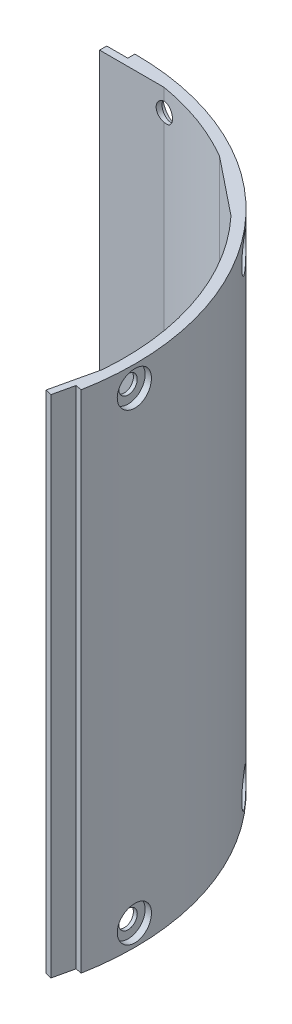
SolidWorks part; units mm, degrees
ref_plane "Спереди" through (0, 0, 0) normal (0, 0, 1) x (1, 0, 0)
ref_plane "Сверху" through (0, 0, 0) normal (0, 1, 0) x (1, 0, 0)
ref_plane "Справа" through (0, 0, 0) normal (1, 0, 0) x (0, 0, -1)
sketch "Эскиз2" plane through (0, 0, 0) normal (0, 1, 0) x (1, 0, 0)
  line L0 (0, -1000) -> (0, 49000) construction
  line L1 (-8.2529, 48.3) -> (8.2529, 48.3) construction
  line L2 (35.7629, 33.4965) -> (24.8621, 42.2241) construction
  line L3 (48.839, -3.9694) -> (45.736, -17.5845) construction
  line L4 (-4, 48.3) -> (8.2529, 48.3)
  line L5 (35.7629, 33.4965) -> (24.8621, 42.2241)
  line L6 (48.839, -3.9694) -> (45.736, -17.5845) construction
  line L7 (-4, 48.3) -> (-4, 49.65)
  line L8 (-4, 49.65) -> (0, 49.65)
  line L10 (-8.2529, 48.3) -> (-4, 48.3) construction
  line L12 (0, 0) -> (47.2875, -10.7769) construction
  line L13 (50.1312, -9.3737) -> (48.9507, -9.1047)
  line L14 (48.9507, -9.1047) -> (48.0618, -13.0047)
  line L15 (48.0618, -13.0047) -> (46.8431, -12.7269)
  line L16 (47.2875, -10.7769) -> (49.725, -11.3324) construction
  line L17 (46.8431, -12.7269) -> (48.839, -3.9694)
  line L19 (0, 49.65) -> (0, 51)
  line L20 (0, 48.3) -> (0, 49.65) construction
  circle A0 centre (0, 0) radius 51 construction
  arc A1 (50.1312, -9.3737) -> (0, 51) centre (0, 0) ccw
  circle A2 centre (0, 0) radius 51 construction
  arc A3 (48.839, -3.9694) -> (35.7629, 33.4965) centre (0, 0) ccw construction
  arc A4 (0, 51) -> (0, -51) centre (0, 0) ccw construction
  arc A5 (48.839, -3.9694) -> (35.7629, 33.4965) centre (0, 0) ccw
  arc A6 (8.2529, 48.3) -> (24.8621, 42.2241) centre (0, 0) cw
  arc A7 (0, -51) -> (49.725, -11.3324) centre (0, 0) ccw construction
  arc A8 (49.725, -11.3324) -> (50.1312, -9.3737) centre (0, 0) ccw construction
  point P25 (48.5063, -11.0547)
  dimension "D1" = 4
extrude "Бобышка-Вытянуть2" add sketch "Эскиз2" along normal up to surface (96 mm away)
ref_plane "Плоскость4" through (12.7171, 0, -36.1271) normal (-0.332, 0, 0.9433) x (0.9433, 0, 0.332)
sketch "Эскиз7" plane through (12.7171, 0, -36.1271) normal (-0.332, 0, 0.9433) x (0.9433, 0, 0.332)
  line L5 (-8.2529, 17) -> (5.2529, 17) construction
  line L6 (-8.2529, 17) -> (5.2529, 17) construction
  line L7 (8.2529, 14) -> (5.2529, 17) construction
  line L8 (8.2529, 14) -> (5.2529, 17)
  line L9 (-8.2529, 0) -> (8.2529, 0) construction
  line L16 (-8.2529, 0) -> (8.2529, 0)
  line L17 (-8.2529, 96) -> (-8.2529, 0) construction
  line L18 (-8.2529, 17) -> (-8.2529, 0) construction
  line L19 (8.7529, 14.2071) -> (8.7529, 0)
  line L20 (8.7529, 14.2071) -> (5.46, 17.5)
  line L21 (8.2529, 14) -> (8.2529, 0) construction
  line L22 (8.2529, 14) -> (8.2529, 0) construction
  line L23 (-8.7529, 17.5) -> (5.46, 17.5)
  line L24 (-8.7529, 17.5) -> (-8.7529, 0)
  line L25 (-8.7529, 0) -> (-8.2529, 0)
  line L26 (8.2529, 0) -> (8.7529, 0)
  dimension "D1" = 0.5
extrude "Вырез-Вытянуть3" cut sketch "Эскиз7" against normal through all contours L16 L26 L19 L20 L23 L24 L25 region at (12.587, 8.6121, -36.1729)
sketch "Эскиз9" plane through (0, 0, -48.3) normal (0, 0, 1) x (1, 0, 0)
  line L4 (8.7529, 0) -> (8.7529, 17.5)
  line L6 (-4, 96) -> (-4, 0) construction
  line L7 (-4, 19.5) -> (-4, 0)
  line L8 (-4, 96) -> (-4, 19.5) construction
  line L9 (-4, 19.5) -> (-6.5, 17) construction
  line L10 (-8.2529, 0) -> (-4, 0) construction
  line L11 (8.7529, 17.5) -> (6.7071, 17.5)
  line L12 (6.7071, 17.5) -> (3.7071, 20.5)
  line L13 (3.7071, 20.5) -> (-3.7071, 20.5)
  line L14 (-8.2529, 0) -> (8.2529, 0)
  line L15 (8.2529, 0) -> (8.2529, 17)
  line L24 (8.2529, 17) -> (6.5, 17)
  line L25 (6.5, 17) -> (3.5, 20)
  line L26 (3.5, 20) -> (-3.5, 20)
  line L28 (-3.7071, 20.5) -> (-4, 20.2071)
  line L29 (-3.5, 20) -> (-6.5, 17)
  line L30 (-6.5, 17) -> (-8.2529, 17)
  line L31 (-8.2529, 17) -> (-8.2529, 0)
  line L32 (-4, 0) -> (8.2529, 0)
  line L33 (8.2529, 0) -> (8.2529, 17) construction
  line L34 (8.2529, 17) -> (6.5, 17) construction
  line L35 (6.5, 17) -> (3.5, 20) construction
  line L36 (3.5, 20) -> (-3.5, 20) construction
  line L37 (-3.5, 20) -> (-4, 19.5)
  line L38 (-6.5, 17) -> (-8.2529, 17) construction
  line L39 (-8.2529, 17) -> (-8.2529, 0) construction
  line L40 (-4, 19.5) -> (-4, 20.2071)
  line L41 (-4, 20.2071) -> (-4.3536, 19.8536) construction
  line L42 (-3.7071, 20.5) -> (-4.3536, 19.8536) construction
  line L43 (8.7529, 0) -> (8.2529, 0)
  line M9 (-8.2529, 0) -> (8.2529, 0)
  line M10 (8.2529, 0) -> (8.2529, 17)
  line M11 (8.2529, 17) -> (6.5, 17)
  line M12 (6.5, 17) -> (3.5, 20)
  line M13 (3.5, 20) -> (-3.5, 20)
  line M14 (-3.5, 20) -> (-6.5, 17)
  dimension "D1" = 0
  dimension "D2" = 0.5
extrude "Вырез-Вытянуть4" cut sketch "Эскиз9" against normal through all contours L7 M14 M9 M10 M11 M12 M13 | L43 L4 L11 L12 L13 L28 L40 M14 M13 M12 M11 M10 region at (8.5029, 0.2414, -48.3) region at (1.9477, 9.6325, -48.3)
sketch "Эскиз10" plane through (0, 12, 0) normal (0, 1, 0) x (1, 0, 0)
  line L0 (-4, 48.3) -> (8.2529, 48.3) construction
  line L1 (-4, 48.3) -> (8.2529, 48.3)
  line L2 (23.8222, 42.8194) -> (20.9924, 43.8155) construction
  line L3 (8.2529, 48.3) -> (20.9924, 43.8155) construction
  line L4 (23.8222, 42.8194) -> (20.9924, 43.8155)
  line L5 (8.2529, 48.3) -> (20.9924, 43.8155)
  line L7 (23.4097, 41.9045) -> (20.6603, 42.8723)
  line L8 (8.082, 47.3) -> (20.6603, 42.8723)
  line L9 (-4, 47.3) -> (8.082, 47.3)
  line L10 (-4, 47.3) -> (-4, 48.3)
  line L11 (24.3547, 41.3624) -> (24.8621, 42.2241) construction
  line L12 (24.3547, 41.3624) -> (26.3116, 41.0636)
  line L13 (24.8621, 42.2241) -> (35.7629, 33.4965) construction
  line L14 (26.3116, 41.0636) -> (24.8621, 42.2241) construction
  line L15 (26.3116, 41.0636) -> (24.8621, 42.2241) construction
  line L16 (26.3116, 41.0636) -> (24.8621, 42.2241)
  arc A0 (24.8621, 42.2241) -> (8.2529, 48.3) centre (0, 0) ccw construction
  arc A1 (24.8621, 42.2241) -> (23.8222, 42.8194) centre (0, 0) ccw
  arc A2 (23.8222, 42.8194) -> (8.2529, 48.3) centre (0, 0) ccw construction
  arc A3 (24.3547, 41.3624) -> (23.4097, 41.9045) centre (0, 0) ccw
  dimension "D2" = 30
  dimension "D1" = 1
extrude "Бобышка-Вытянуть7" add sketch "Эскиз10" along normal blind 10
sketch "Эскиз13" plane through (0, 22, 0) normal (0, 1, 0) x (1, 0, 0)
  line L0 (23.8222, 42.8194) -> (8.2529, 48.3) construction
  line L1 (23.8222, 42.8194) -> (8.2529, 48.3)
  arc A0 (24.8621, 42.2241) -> (8.2529, 48.3) centre (0, 0) ccw construction
  arc A1 (24.8621, 42.2241) -> (8.2529, 48.3) centre (0, 0) ccw
  line M2 (23.8222, 42.8194) -> (8.2529, 48.3)
extrude "Бобышка-Вытянуть8" add sketch "Эскиз13" against normal up to surface (4.5 mm away) contours A1 M2 region at (16.1306, 22, -45.824) up to face at (13.0597, 17.5, -47.6707)
sketch "Эскиз14" plane through (0, 17.5, 0) normal (0, -1, 0) x (1, 0, 0)
  line L0 (21.3189, -44.1192) -> (21.1877, -43.7468)
  line L1 (21.1877, -43.7468) -> (8.2529, -48.3) construction
  line L4 (21.9869, -46.0171) -> (21.3189, -44.1192)
  line L5 (23.8222, -42.8194) -> (8.2529, -48.3)
  line L6 (8.2529, -48.3) -> (6.7071, -48.3)
  line L7 (6.7071, -48.3) -> (6.7071, -50.557)
  line L8 (21.9869, -46.0171) -> (21.3189, -44.1192)
  line L9 (23.8222, -42.8194) -> (21.1877, -43.7468)
  line L10 (8.2529, -48.3) -> (6.7071, -48.3) construction
  line L11 (6.7071, -48.3) -> (6.7071, -50.557) construction
  arc A2 (6.7071, -50.557) -> (21.9869, -46.0171) centre (0, 0) ccw
  arc A3 (21.3189, -44.1192) -> (23.8222, -42.8194) centre (0, 0) ccw
  arc A4 (6.7071, -50.557) -> (21.9869, -46.0171) centre (0, 0) ccw construction
  arc A5 (21.3189, -44.1192) -> (23.8222, -42.8194) centre (0, 0) ccw
  dimension "D1" = 0
extrude "Бобышка-Вытянуть9" add sketch "Эскиз14" along normal up to surface contours A5 L9 L0 up to face at (23.2708, 15.6229, -44.011)
chamfer "Фаска1" distance 1 angle 45 4 edges at (2.041, 22, -47.3) (15.7459, 22, -44.6022) (23.8837, 22, -41.6361) (25.3331, 22, -41.213)
ref_plane "Плоскость5" through (51, 0, 0) normal (1, 0, 0) x (0, 0, -1)
sketch "Эскиз15" plane through (51, 0, 0) normal (1, 0, 0) x (0, 0, -1)
  line L0 (0, -1000) -> (0, 49000) construction
  circle A0 centre (0, 4) radius 3.25
  point P5 (0, 6.0834)
  dimension "D1" = 6.5
  dimension "D2" = 4
extrude "Вырез-Вытянуть5" cut sketch "Эскиз15" against normal blind 1.3
sketch "Эскиз16" plane through (49.7, 0, 0) normal (1, 0, 0) x (0, 0, -1)
  circle A0 centre (0, 4) radius 3.25 construction
  circle A1 centre (0, 4) radius 3.25 construction
  circle A2 centre (0, 4) radius 1.75
  dimension "D1" = 3.5
extrude "Вырез-Вытянуть6" cut sketch "Эскиз16" against normal through all
pattern_circular "Круговой массив3" count 3 every 20 about axis through (0, 0, 0) along (0, 1, 0) skipping 1 of "Вырез-Вытянуть5", "Вырез-Вытянуть6"
sketch "Эскиз17" plane through (51, 0, 0) normal (1, 0, 0) x (0, 0, -1)
  line L0 (0, -1000) -> (0, 49000) construction
  line L1 (51, 96) -> (-9.3737, 96) construction
  circle A0 centre (0, 92) radius 3.25
  circle A1 centre (0, 4) radius 3.25 construction
  dimension "D1" = 4
extrude "Вырез-Вытянуть7" cut sketch "Эскиз17" against normal blind 1.3
sketch "Эскиз18" plane through (49.7, 0, 0) normal (1, 0, 0) x (0, 0, -1)
  circle A0 centre (0, 92) radius 3.25 construction
  circle A1 centre (0, 92) radius 3.25 construction
  circle A2 centre (0, 92) radius 1.75
  circle A3 centre (0, 4) radius 1.75 construction
extrude "Вырез-Вытянуть8" cut sketch "Эскиз18" against normal through all
pattern_circular "Круговой массив5" count 5 every 20 about axis through (0, 96, 0) along (0, 1, 0) skipping 1, 3 of "Вырез-Вытянуть8", "Вырез-Вытянуть7"
